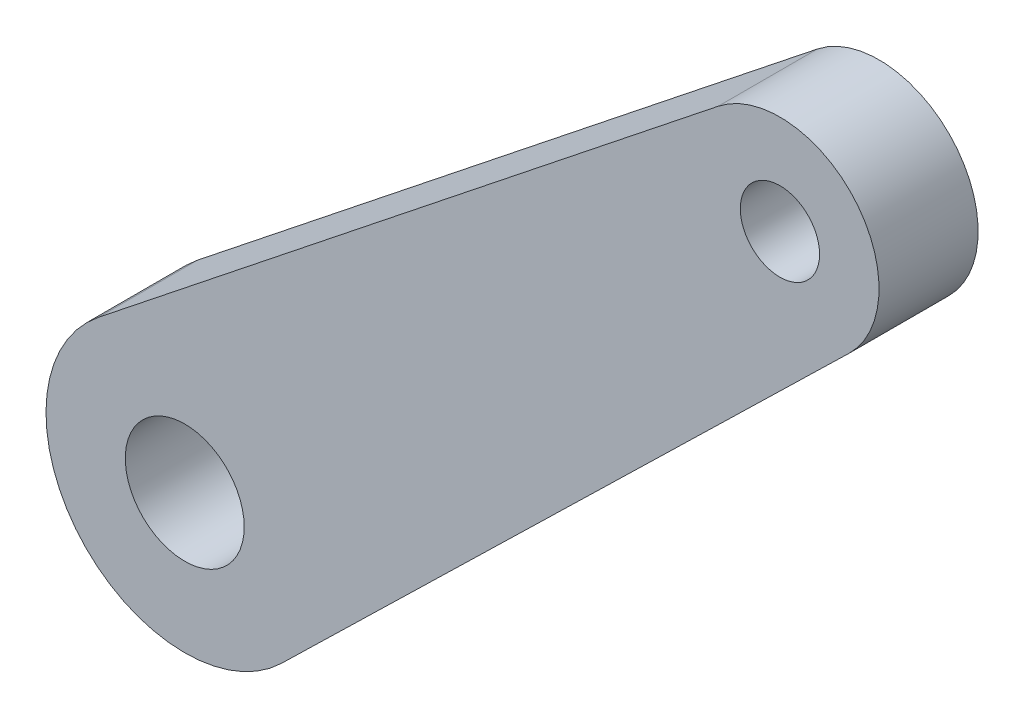
SolidWorks part; units mm, degrees
ref_plane "Front Plane" through (0, 0, 0) normal (0, 0, 1) x (1, 0, 0)
ref_plane "Top Plane" through (0, 0, 0) normal (0, 1, 0) x (1, 0, 0)
ref_plane "Right Plane" through (0, 0, 0) normal (1, 0, 0) x (0, 0, -1)
sketch "Sketch1" plane through (0, 0, 0) normal (0, 0, 1) x (1, 0, 0)
  line L0 (-54.3561, 23.4794) -> (-23.0841, 48.3403)
  line L1 (-16.4858, 40.8429) -> (-45.1184, 12.983)
  circle A0 centre (-50, 18) radius 3 construction
  circle A1 centre (-19.9726, 44.4264) radius 2 construction
  circle A2 centre (-50, 18) radius 3
  circle A3 centre (-19.9726, 44.4264) radius 2
  arc A4 (-23.0841, 48.3403) -> (-16.4858, 40.8429) centre (-19.9726, 44.4264) cw
  arc A5 (-45.1184, 12.983) -> (-54.3561, 23.4794) centre (-50, 18) cw
  dimension "D1" = 5
  dimension "D2" = 7
extrude "Boss-Extrude1" add sketch "Sketch1" along normal blind 5 from offset 10
